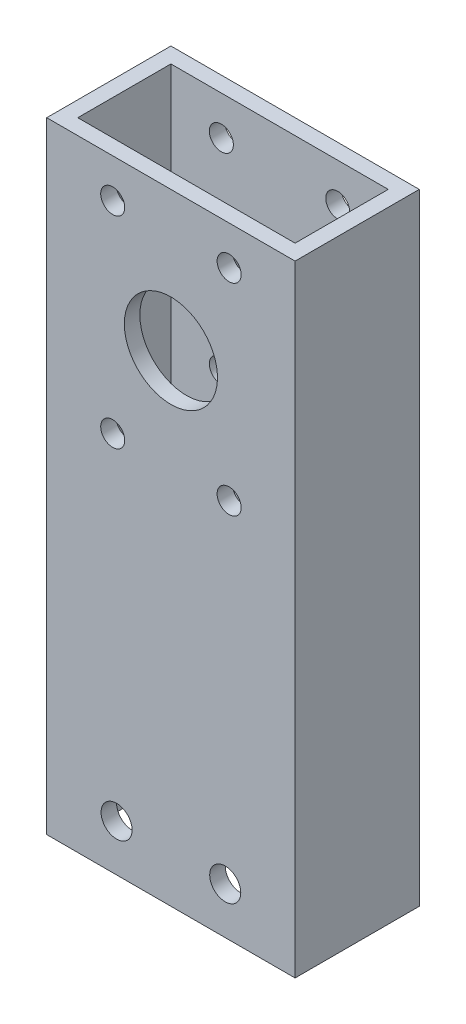
SolidWorks part; units mm, degrees
material "6061-T6 (SS)"
ref_plane "Front" through (0, 0, 0) normal (0, 0, 1) x (1, 0, 0)
ref_plane "Top" through (0, 0, 0) normal (0, 1, 0) x (1, 0, 0)
ref_plane "Right" through (0, 0, 0) normal (1, 0, 0) x (0, 0, -1)
sketch "Sketch1" plane through (0, 0, 0) normal (0, 1, 0) x (1, 0, 0)
  line L1 (-25.4, -12.7) -> (25.4, -12.7)
  line L2 (-25.4, -12.7) -> (-25.4, 12.7)
  line L3 (-25.4, 12.7) -> (25.4, 12.7)
  line L4 (25.4, -12.7) -> (25.4, 12.7)
  line L5 (-25.4, -12.7) -> (25.4, 12.7) construction
  line L6 (-25.4, 12.7) -> (25.4, -12.7) construction
  point P0 (0, 0)
  dimension "D1" = 25.4
  dimension "D2" = 50.8
extrude "Extrude-Thin1" add sketch "Sketch1" along normal blind 127 thin thin type one direction reverse wall 3.175
sketch "Sketch2" plane through (0, 0, -12.7) normal (0, 0, -1) x (-1, 0, 0)
  line L0 (0, 127) -> (0, 95.25)
  line L1 (-25.4, 127) -> (25.4, 127) construction
  line L3 (0, 85.725) -> (0, 104.775) construction
  circle A1 centre (0, 95.25) radius 23.8125
  circle A3 centre (0, 95.25) radius 9.525
  point P12 (0, 95.25)
  dimension "D1" = 19.05
  dimension "D3" = 47.625
  dimension "D2" = 31.75
hole_wizard "#10 (0.1935) Diameter Hole2" positions "Sketch5" profile "Sketch6" hole size "#10" standard "ANSI Inch" end condition through all
sketch "Sketch5" plane through (0, 0, -12.7) normal (0, 0, -1) x (-1, 0, 0)
  line L0 (0, 127) -> (0, 98.425)
  line L1 (-25.4, 127) -> (25.4, 127) construction
  line L3 (-11.9063, 119.0472) -> (11.9063, 119.0472)
  line L4 (-11.9063, 119.0472) -> (-11.9063, 77.8028)
  line L5 (-11.9063, 77.8028) -> (11.9063, 77.8028)
  line L6 (11.9063, 119.0472) -> (11.9063, 77.8028)
  circle A0 centre (0, 98.425) radius 23.8125
  point P21 (-11.9063, 119.0472)
  point P22 (11.9063, 119.0472)
  point P24 (11.9063, 77.8028)
  point P25 (-11.9062, 77.8028)
  dimension "D1" = 47.625
  dimension "D2" = 28.575
  dimension "D3" = 23.8125
sketch "Sketch6" plane through (11.9062, 77.8028, -12.7) normal (1, 0, 0) x (0, 1, 0)
  line L0 (0, 0) -> (0, 25.4)
  line L1 (0, 25.4) -> (2.4574, 25.4)
  line L2 (2.4574, 25.4) -> (2.4574, 0)
  line L5 (2.4574, 0) -> (0, 0)
  line L11 (0, -6.35) -> (0, 107.95) construction
  dimension "Thru Hole Dia." = 4.9149
  dimension "Thru Hole Depth" = 25.4
sketch "Sketch7" plane through (0, 0, -12.7) normal (0, 0, -1) x (-1, 0, 0)
  line L0 (-11.9063, 119.0472) -> (11.9063, 77.8028) construction
  circle A1 centre (0, 98.425) radius 9.525
  point P9 (0, 98.425)
  dimension "D1" = 19.05
extrude "Cut-Extrude2" cut sketch "Sketch7" against normal through all both
hole_wizard "1/4 (0.25) Diameter Hole1" positions "Sketch8" profile "Sketch9" hole size "1/4" standard "ANSI Inch" end condition through all
sketch "Sketch8" plane through (0, 0, 12.7) normal (0, 0, 1) x (1, 0, 0)
  line L2 (-25.4, 127) -> (-25.4, 0) construction
  line L4 (-25.4, 0) -> (25.4, 0) construction
  point P0 (-11.1125, 9.525)
  point P2 (11.1125, 9.525)
  point P14 (-109.1715, 68.7854)
  dimension "D1" = 22.225
  dimension "D2" = 14.2875
  dimension "D3" = 9.525
sketch "Sketch9" plane through (-11.1125, 9.525, 12.7) normal (1, 0, 0) x (0, -1, 0)
  line L0 (0, 0) -> (0, 25.4)
  line L1 (0, 25.4) -> (3.175, 25.4)
  line L2 (3.175, 25.4) -> (3.175, 0)
  line L5 (3.175, 0) -> (0, 0)
  line L11 (0, -6.35) -> (0, 107.95) construction
  dimension "Thru Hole Dia." = 6.35
  dimension "Thru Hole Depth" = 25.4
